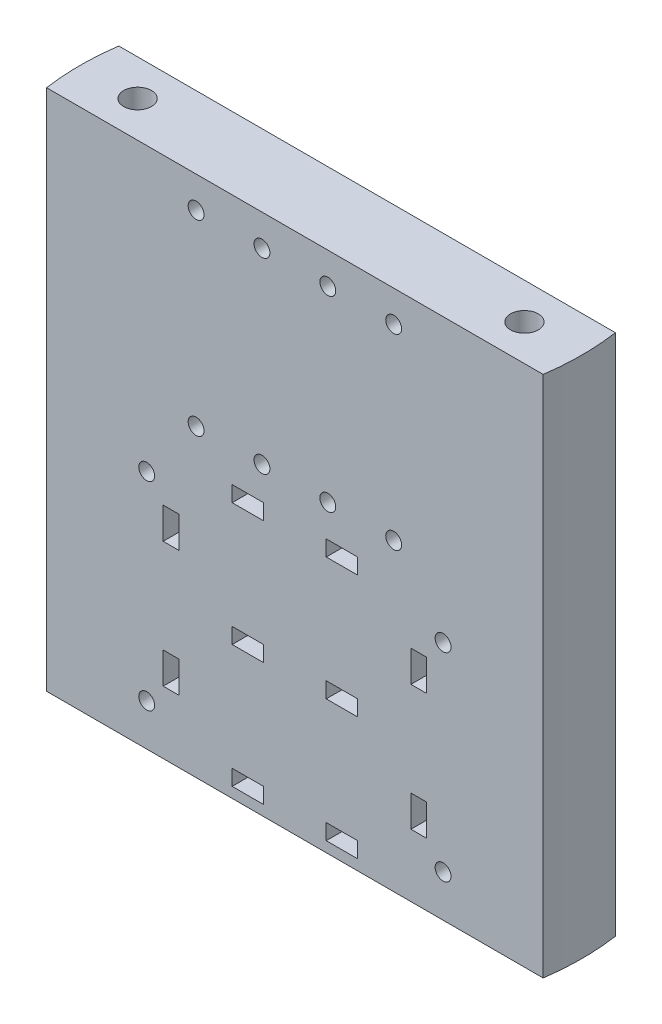
SolidWorks part; units mm, degrees
ref_plane "Front Plane" through (0, 0, 0) normal (0, 0, 1) x (1, 0, 0)
ref_plane "Top Plane" through (0, 0, 0) normal (0, 1, 0) x (1, 0, 0)
ref_plane "Right Plane" through (0, 0, 0) normal (1, 0, 0) x (0, 0, -1)
sketch "Sketch1" plane through (0, 0, 0) normal (0, 1, 0) x (1, 0, 0)
  line L0 (-60.325, 8.7759) -> (60.325, 8.7759)
  line L1 (-60.325, -8.7759) -> (60.325, -8.7759)
  arc A0 (60.325, -8.7759) -> (60.325, 8.7759) centre (0, 0) ccw
  arc A1 (-60.325, 8.7759) -> (-60.325, -8.7759) centre (0, 0) ccw
  point P1 (0, 8.7759)
  dimension "D1" = 121.92
  dimension "D4" = 60.96
  dimension "D2" = 120.65
  dimension "D3" = 120.65
  dimension "D5" = 8.7759
extrude "Boss-Extrude1" add sketch "Sketch1" along normal blind 127 contours L1 | L1 | L1 A0 L0 A1 region at (0, 0, 0)
sketch "Sketch2" plane through (0, 0, 0) normal (0, 1, 0) x (1, 0, 0)
  circle A0 centre (0, 0) radius 61.595
  dimension "D1" = 123.19
sketch "Sketch3" plane through (0, 0, 0) normal (0, 1, 0) x (1, 0, 0)
  circle A0 centre (0, 0) radius 63.5
  dimension "D1" = 127
ref_plane "Raft Top" through (0, 0, 9.9465) normal (0, 0, -1) x (-1, 0, 0)
sketch "Sketch10" plane through (0, 0, -8.7759) normal (0, 0, -1) x (-1, 0, 0)
  line L0 (-32.004, 2.54) -> (-32.004, 66.04)
  line L5 (-32.004, 66.04) -> (32.004, 66.04)
  line L10 (32.004, 66.04) -> (32.004, 2.54)
  line L11 (32.004, 2.54) -> (-32.004, 2.54)
  line L16 (60.325, 127) -> (60.325, 0) construction
  line L17 (61.595, 0) -> (-61.595, 0) construction
  line L18 (-60.325, 127) -> (-60.325, 0) construction
  dimension "D1" = 28.321
  dimension "D2" = 2.54
  dimension "D3" = 28.321
  dimension "D4" = 63.5
  dimension "D5" = 64.008
sketch "Sketch13" plane through (0, 127, 0) normal (0, 1, 0) x (1, 0, 0)
  line L2 (60.325, 8.7759) -> (-60.325, 8.7759)
  line L3 (-60.325, -8.7759) -> (60.325, -8.7759)
  line L4 (60.325, 8.7759) -> (-60.325, 8.7759)
  line L5 (-60.325, -8.7759) -> (60.325, -8.7759)
  line L6 (-46.99, 8.7759) -> (-46.99, -8.7759) construction
  line L7 (0, -69.85) -> (0, 69.85) construction
  line L8 (-32.004, 8.7759) -> (32.004, 8.7759) construction
  arc A2 (-60.325, 8.7759) -> (-60.325, -8.7759) centre (0, 0) ccw
  arc A3 (60.325, -8.7759) -> (60.325, 8.7759) centre (0, 0) ccw
  arc A4 (-60.325, 8.7759) -> (-60.325, -8.7759) centre (0, 0) ccw
  arc A5 (60.325, -8.7759) -> (60.325, 8.7759) centre (0, 0) ccw
  point P10 (-46.99, 0)
  point P13 (46.99, 0)
  dimension "D2" = 46.99
  dimension "D1" = 0
hole_wizard "Tap Drill for 1/4 Helicoil1" positions "Sketch14" profile "Sketch15" hole size "1/4-20" standard "ANSI Inch" end condition through all
sketch "Sketch14" plane through (0, 127, 0) normal (0, 1, 0) x (1, 0, 0)
  point P0 (-46.99, 0)
  point P3 (46.99, 0)
sketch "Sketch15" plane through (-46.99, 127, 0) normal (1, 0, 0) x (0, 0, 1)
  line L0 (0, 0) -> (0, 127)
  line L1 (0, 127) -> (3.3782, 127)
  line L2 (3.3782, 127) -> (3.3782, 0)
  line L5 (3.3782, 0) -> (0, 0)
  line L11 (0, -6.35) -> (0, 107.95) construction
  dimension "Thru Hole Dia." = 6.7564
  dimension "Thru Hole Depth" = 127
sketch "Sketch16" plane through (0, 0, 9.9465) normal (0, 0, -1) x (-1, 0, 0)
  line L0 (60.325, 127) -> (-60.325, 127) construction
  line L3 (0, 69.85) -> (0, -69.85) construction
  point P0 (-24.003, 119.38)
  point P1 (-8.001, 119.38)
  point P2 (-8.001, 73.914)
  point P3 (-24.003, 73.914)
  point P28 (8.001, 73.914)
  point P29 (24.003, 73.914)
  point P30 (8.001, 119.38)
  point P31 (24.003, 119.38)
  dimension "D1" = 16.002
  dimension "D2" = 45.466
  dimension "D3" = 8.001
  dimension "D4" = 7.62
sketch "Sketch19" plane through (0, 0, -8.7759) normal (0, 0, -1) x (-1, 0, 0)
  line L0 (0, 66.04) -> (0, 2.54) construction
  line L3 (-32.004, 34.29) -> (32.004, 34.29) construction
  line L8 (-15.24, 36.195) -> (-7.62, 36.195)
  line L9 (-15.24, 36.195) -> (-15.24, 32.385)
  line L10 (-15.24, 32.385) -> (-7.62, 32.385)
  line L11 (-7.62, 36.195) -> (-7.62, 32.385)
  line L19 (32.004, 45.72) -> (28.194, 45.72)
  line L20 (-15.24, 66.04) -> (-7.62, 66.04)
  line L21 (-15.24, 66.04) -> (-15.24, 62.23)
  line L22 (-15.24, 62.23) -> (-7.62, 62.23)
  line L23 (-7.62, 66.04) -> (-7.62, 62.23)
  line L36 (15.24, 62.23) -> (7.62, 62.23)
  line L37 (7.62, 66.04) -> (7.62, 62.23)
  line L38 (15.24, 66.04) -> (7.62, 66.04)
  line L39 (15.24, 66.04) -> (15.24, 62.23)
  line L40 (-15.24, 6.35) -> (-7.62, 6.35)
  line L41 (-7.62, 2.54) -> (-7.62, 6.35)
  line L42 (-15.24, 2.54) -> (-7.62, 2.54)
  line L43 (-15.24, 2.54) -> (-15.24, 6.35)
  line L44 (15.24, 2.54) -> (15.24, 6.35)
  line L45 (15.24, 2.54) -> (7.62, 2.54)
  line L46 (7.62, 2.54) -> (7.62, 6.35)
  line L47 (15.24, 6.35) -> (7.62, 6.35)
  line L48 (-32.004, 53.34) -> (-28.194, 53.34)
  line L49 (-32.004, 53.34) -> (-32.004, 45.72)
  line L50 (-32.004, 45.72) -> (-28.194, 45.72)
  line L51 (-28.194, 53.34) -> (-28.194, 45.72)
  line L52 (28.194, 53.34) -> (28.194, 45.72)
  line L53 (32.004, 53.34) -> (28.194, 53.34)
  line L54 (32.004, 53.34) -> (32.004, 45.72)
  line L55 (32.004, 15.24) -> (32.004, 22.86)
  line L56 (32.004, 15.24) -> (28.194, 15.24)
  line L57 (28.194, 15.24) -> (28.194, 22.86)
  line L58 (32.004, 22.86) -> (28.194, 22.86)
  line L59 (-32.004, 22.86) -> (-28.194, 22.86)
  line L60 (-28.194, 15.24) -> (-28.194, 22.86)
  line L61 (-32.004, 15.24) -> (-28.194, 15.24)
  line L62 (-32.004, 15.24) -> (-32.004, 22.86)
  line L63 (-32.004, 66.04) -> (32.004, 66.04) construction
  line L64 (32.004, 66.04) -> (32.004, 2.54) construction
  line L65 (32.004, 2.54) -> (-32.004, 2.54) construction
  line L66 (-32.004, 2.54) -> (-32.004, 66.04) construction
  line L67 (7.62, 36.195) -> (7.62, 32.385)
  line L68 (15.24, 32.385) -> (7.62, 32.385)
  line L69 (15.24, 36.195) -> (15.24, 32.385)
  line L70 (15.24, 36.195) -> (7.62, 36.195)
  point P10 (0, 34.29)
  point P12 (-15.24, 36.195)
  point P22 (-15.24, 66.04)
  point P41 (-32.004, 53.34)
  dimension "D1" = 7.62
  dimension "D2" = 3.81
  dimension "D3" = 15.24
  dimension "D4" = 1.905
  dimension "D5" = 15.24
  dimension "D6" = 7.62
  dimension "D7" = 3.81
  dimension "D8" = 19.05
  dimension "D9" = 3.81
  dimension "D10" = 7.62
hole_wizard "#8 Clearance Hole1" positions "Sketch20" profile "Sketch21" hole size "#8" standard "ANSI Inch" end condition through all
sketch "Sketch20" plane through (0, 0, -8.7759) normal (0, 0, -1) x (-1, 0, 0)
  point P3 (-8.001, 119.38)
  point P9 (-8.001, 73.914)
  point P12 (8.001, 73.914)
  point P21 (8.001, 119.38)
sketch "Sketch21" plane through (8.001, 119.38, -8.7759) normal (1, 0, 0) x (0, 1, 0)
  line L0 (0, 0) -> (0, 17.5517)
  line L1 (0, 17.5517) -> (1.9304, 17.5517)
  line L2 (1.9304, 17.5517) -> (1.9304, 0)
  line L5 (1.9304, 0) -> (0, 0)
  line L11 (0, -6.35) -> (0, 107.95) construction
  dimension "Thru Hole Dia." = 3.8608
  dimension "Thru Hole Depth" = 17.5517
extrude "Cut-Extrude3" cut sketch "Sketch19" against normal through all
hole_wizard "#8 Clearance Hole2" positions "Sketch22" profile "Sketch24" hole size "#8" standard "ANSI Inch" end condition through all
sketch "Sketch22" plane through (0, 0, -8.7759) normal (0, 0, -1) x (-1, 0, 0)
  point P0 (-24.003, 119.38)
  point P3 (-24.003, 73.914)
  point P6 (24.003, 73.914)
  point P9 (24.003, 119.38)
sketch "Sketch24" plane through (24.003, 119.38, -8.7759) normal (1, 0, 0) x (0, 1, 0)
  line L0 (0, 0) -> (0, 17.5517)
  line L1 (0, 17.5517) -> (1.9304, 17.5517)
  line L2 (1.9304, 17.5517) -> (1.9304, 0)
  line L5 (1.9304, 0) -> (0, 0)
  line L11 (0, -6.35) -> (0, 107.95) construction
  dimension "Thru Hole Dia." = 3.8608
  dimension "Thru Hole Depth" = 17.5517
sketch "Sketch29" plane through (0, 0, -8.7759) normal (0, 0, -1) x (-1, 0, 0)
  line L0 (60.325, 127) -> (60.325, 0) construction
  line L1 (-40.005, 66.04) -> (40.005, 66.04)
  line L2 (-40.005, 66.04) -> (-40.005, 2.54)
  line L3 (-40.005, 2.54) -> (40.005, 2.54)
  line L4 (40.005, 66.04) -> (40.005, 2.54)
  line L5 (-60.325, 127) -> (-60.325, 0) construction
  line L6 (61.595, 0) -> (-61.595, 0) construction
  line L7 (-40.005, 34.29) -> (40.005, 34.29) construction
  line L10 (32.004, 53.34) -> (40.005, 53.34) construction
  line L12 (32.004, 66.04) -> (32.004, 2.54) construction
  line L13 (0, 69.85) -> (0, -69.85) construction
  point P8 (36.0045, 58.42)
  point P20 (36.0045, 53.34)
  point P24 (36.0045, 10.16)
  point P28 (-36.0045, 58.42)
  point P30 (-36.0045, 10.16)
  dimension "D1" = 20.32
  dimension "D2" = 20.32
  dimension "D3" = 2.54
  dimension "D4" = 63.5
  dimension "D5" = 80.01
  dimension "D6" = 7.62
  dimension "D7" = 12.7
hole_wizard "#8 Clearance Hole3" positions "Sketch34" profile "Sketch35" hole size "#8" standard "ANSI Inch" end condition through all
sketch "Sketch34" plane through (0, 0, -8.7759) normal (0, 0, -1) x (-1, 0, 0)
  point P0 (-36.0045, 58.42)
  point P3 (-36.0045, 10.16)
  point P6 (36.0045, 10.16)
  point P9 (36.0045, 58.42)
sketch "Sketch35" plane through (36.0045, 58.42, -8.7759) normal (1, 0, 0) x (0, 1, 0)
  line L0 (0, 0) -> (0, 17.5517)
  line L1 (0, 17.5517) -> (1.9304, 17.5517)
  line L2 (1.9304, 17.5517) -> (1.9304, 0)
  line L5 (1.9304, 0) -> (0, 0)
  line L11 (0, -6.35) -> (0, 107.95) construction
  dimension "Thru Hole Dia." = 3.8608
  dimension "Thru Hole Depth" = 17.5517
extrude "Cut-Extrude4" cut sketch "Sketch29" against normal blind 5.08
